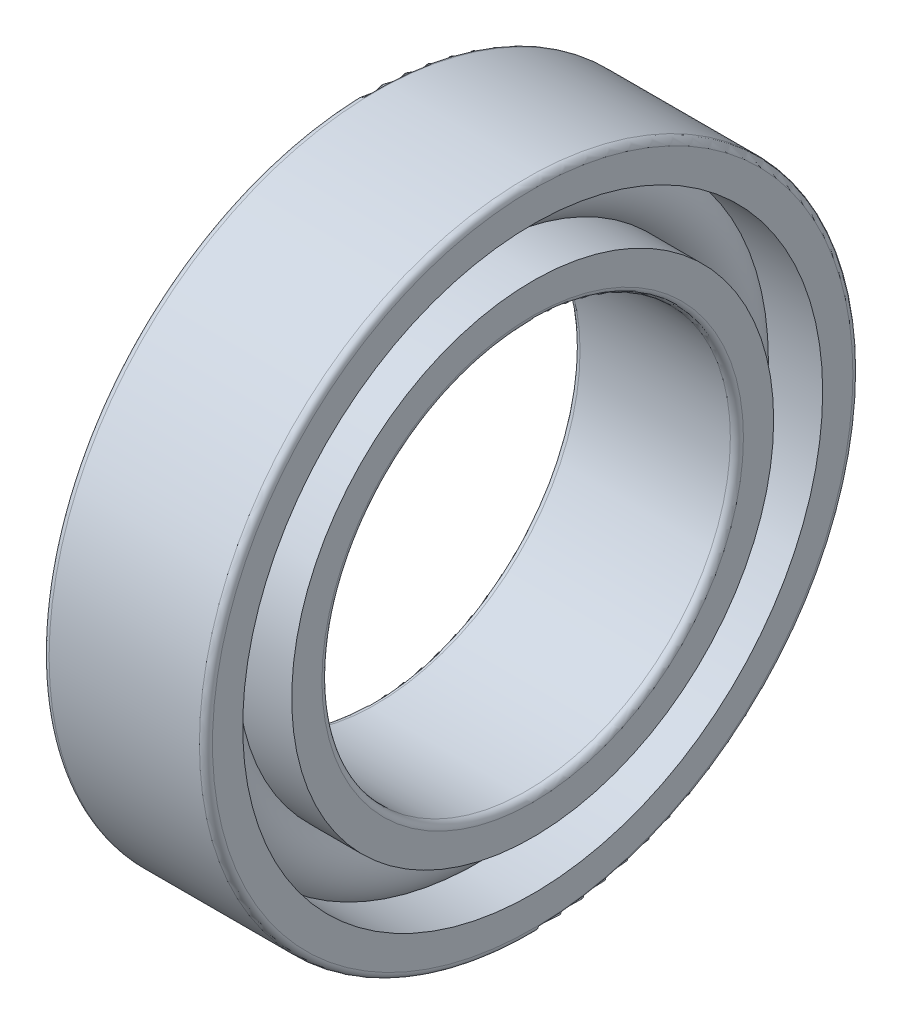
SolidWorks part; units mm, degrees
ref_plane "Plane1" through (0, 0, 0) normal (0, 0, 1) x (1, 0, 0)
ref_plane "Plane2" through (0, 0, 0) normal (0, 1, 0) x (1, 0, 0)
ref_plane "Plane3" through (0, 0, 0) normal (1, 0, 0) x (0, 0, -1)
other "Configuration Table"
sketch "Clipboard" plane through (0, 0, 0) normal (0, 0, 1) x (1, 0, 0)
  line L0 (-10, 0) -> (10, 0) construction
  line L1 (0, 0) -> (22.3471, -0.7804)
  line L2 (0, 0) -> (3.248, 0.1134)
  line L3 (0, 0) -> (22.3471, -0.7804)
  line L4 (0, 0) -> (-22.3573, -0.3902)
  dimension "BallCLRad" = 3.25
sketch "CagSpiSke" plane through (0, 0, 0) normal (0, 0, 1) x (1, 0, 0)
  line L0 (0.045, 3.175) -> (0.045, 3.325)
  line L1 (0.045, 3.325) -> (-0.045, 3.325)
  line L2 (-0.045, 3.325) -> (-0.045, 3.175)
  line L3 (-0.045, 3.175) -> (0.045, 3.175)
  line L4 (-20.6375, 0) -> (20.6375, 0) construction
  line L5 (0, 0) -> (0, 23.7692) construction
  dimension "OD" = 6.65
  dimension "ID" = 6.35
revolve "CageSpine" add sketch "CagSpiSke" angle 0.001 about L4 reverse direction yes
ref_axis "Axis1" through (-50, 0, 0) along (1, 0, 0)
sketch "CagBalSke" plane through (0, 0, 0) normal (0, 0, 1) x (1, 0, 0)
  line L0 (-0.495, 3.25) -> (0.495, 3.25)
  line L1 (-1.905, 3.25) -> (1.905, 3.25) construction
  line L2 (-10, 0) -> (10, 0) construction
  line L3 (0, 0) -> (0, 24) construction
  arc A0 (0.495, 3.25) -> (-0.495, 3.25) centre (0, 3.25) cw
  dimension "BallCLRad" = 3.25
revolve "CageBall" [suppressed] add sketch "CagBalSke" angle 360 about L1 reverse direction yes
pattern_circular "CageBalls" [suppressed] count 2 every 180 about axis through (-50, 0, 0) along (1, 0, 0)
sketch "CagTrmODSke" plane through (0, 0, 0) normal (0, 0, 1) x (1, 0, 0)
  line L0 (0.496, 3.325) -> (0.496, 3.746)
  line L1 (0.496, 3.746) -> (-0.496, 3.746)
  line L2 (-0.496, 3.746) -> (-0.496, 3.325)
  line L3 (-0.496, 3.325) -> (0.496, 3.325)
  line L4 (-20.6375, 0) -> (20.6375, 0) construction
  line L5 (0, 0) -> (0, 25) construction
  dimension "Width" = 0.992
  dimension "ID" = 6.65
  dimension "OD" = 7.492
revolve "CageTrimOD" [suppressed] cut sketch "CagTrmODSke" angle 360 about L4 reverse direction yes
sketch "CagTrmIDSke" plane through (0, 0, 0) normal (0, 0, 1) x (1, 0, 0)
  line L0 (0.496, 2.756) -> (0.496, 3.175)
  line L1 (0.496, 3.175) -> (-0.496, 3.175)
  line L2 (-0.496, 3.175) -> (-0.496, 2.756)
  line L3 (-0.496, 2.756) -> (0.496, 2.756)
  line L4 (-20.6375, 0) -> (20.6375, 0) construction
  line L5 (0, 0) -> (0, 25) construction
  dimension "Width" = 0.992
  dimension "ID" = 5.512
  dimension "OD" = 6.35
revolve "CageTrimID" [suppressed] cut sketch "CagTrmIDSke" angle 360 about L4 reverse direction yes
sketch "BalSimSke" plane through (0, 0, 0) normal (0, 0, 1) x (1, 0, 0)
  line L0 (-10, 0) -> (10, 0) construction
  line L1 (-10, 3.25) -> (10, 3.25) construction
  line L2 (0, 0) -> (0, 23) construction
  circle A0 centre (0, 3.25) radius 0.45
  dimension "BallCLRad" = 3.25
  dimension "Ball_diameter" = 0.9
revolve "BallsSimplified" add sketch "BalSimSke" angle 360 about L0
sketch "BalDetSke" plane through (0, 0, 0) normal (0, 0, 1) x (1, 0, 0)
  line L0 (-0.45, 3.25) -> (0.45, 3.25)
  line L1 (-1.905, 3.25) -> (1.905, 3.25) construction
  line L2 (0, 0) -> (0, 25) construction
  arc A0 (0.45, 3.25) -> (-0.45, 3.25) centre (0, 3.25) cw
  dimension "BallCLRad" = 3.25
  dimension "Ball_diameter" = 0.9
revolve "BallDetailed" [suppressed] add sketch "BalDetSke" angle 360 about L1 reverse direction yes
sketch "InnRacSke" plane through (0, 0, 0) normal (0, 0, 1) x (1, 0, 0)
  line L0 (-0.301, 2.95) -> (-1, 2.95)
  line L1 (-1, 2.95) -> (-1, 2.58)
  line L2 (-0.92, 2.5) -> (0.92, 2.5)
  line L3 (1, 2.58) -> (1, 2.95)
  line L4 (1, 2.95) -> (0.301, 2.95)
  line L5 (-20.6375, 0) -> (20.6375, 0) construction
  line L6 (0, 0) -> (0, 30) construction
  arc A0 (-1, 2.58) -> (-0.92, 2.5) centre (-0.92, 2.58) ccw
  arc A1 (0.92, 2.5) -> (1, 2.58) centre (0.92, 2.58) ccw
  arc A2 (0.301, 2.95) -> (-0.301, 2.95) centre (0, 3.25) cw
  dimension "BallCLRad" = 3.25
  dimension "Fillet_radius" = 0.08
  dimension "Ball_diameter" = 0.85
  dimension "ID" = 5
  dimension "OD" = 5.9
  dimension "Width" = 2
revolve "InnerRace" add sketch "InnRacSke" angle 360 about L5 reverse direction yes
sketch "OutRacSke" plane through (0, 0, 0) normal (0, 0, 1) x (1, 0, 0)
  line L0 (-0.301, 3.55) -> (-1, 3.55)
  line L1 (-1, 3.55) -> (-1, 3.92)
  line L2 (-0.92, 4) -> (0.92, 4)
  line L3 (1, 3.92) -> (1, 3.55)
  line L4 (1, 3.55) -> (0.301, 3.55)
  line L5 (-20.6375, 0) -> (20.6375, 0) construction
  line L6 (0, 0) -> (0, 30) construction
  arc A0 (-1, 3.92) -> (-0.92, 4) centre (-0.92, 3.92) cw
  arc A1 (0.92, 4) -> (1, 3.92) centre (0.92, 3.92) cw
  arc A2 (0.301, 3.55) -> (-0.301, 3.55) centre (0, 3.25) ccw
  dimension "BallCLRad" = 3.25
  dimension "Fillet_radius" = 0.08
  dimension "Ball_diameter" = 0.85
  dimension "Width" = 2
revolve "OuterRace" add sketch "OutRacSke" angle 360 about L5 reverse direction yes
pattern_circular "BallsDetailed" [suppressed] count 2 every 180 about axis through (-50, 0, 0) along (1, 0, 0)
equation "\"BallCLRad@Clipboard\" = ( \"OD@OutRacSke\" + \"ID@InnRacSke\" ) / 4"
equation "\"BallCLRad@BalSimSke\" = \"BallCLRad@Clipboard\""
equation "\"BallCLRad@BalDetSke\" = \"BallCLRad@Clipboard\""
equation "\"BallCLRad@InnRacSke\" = \"BallCLRad@Clipboard\""
equation "\"BallCLRad@OutRacSke\" = \"BallCLRad@Clipboard\""
equation "\"Ball_diameter@InnRacSke\" = \"Ball_diameter@BalDetSke\" - 0.05"
equation "\"Ball_diameter@OutRacSke\" = \"Ball_diameter@BalDetSke\" - 0.05"
equation "\"Ball_diameter@BalSimSke\" = \"Ball_diameter@BalDetSke\""
equation "\"Width@OutRacSke\" = \"Width@InnRacSke\""
equation "\"Fillet_radius@OutRacSke\" = \"Fillet_radius@InnRacSke\""
equation "\"Max_count@Clipboard\" = int( 3.14159265 / atn(( \"Ball_diameter@BalDetSke\" / 2) / sqr( \"BallCLRad@Clipboard\"  *  \"BallCLRad@Clipboard\" - ( \"Ball_diameter@BalDetSke\" / 2) *  ( \"Ball_diameter@BalDetSke\" / 2))))"
equation "\"Max_count@Clipboard\" = ((sgn( \"Max_count@Clipboard\" - \"Count@Clipboard\" )-1)*( \"Max_count@Clipboard\" - \"Count@Clipboard\" ))/-2+ \"Count@Clipboard\""
equation "\"Count@BallsDetailed\" = int( \"Show_count@Clipboard\" ) "
equation "\"Count@BallsDetailed\" = ((sgn( \"Count@BallsDetailed\" - \"Max_count@Clipboard\" )-1)*( \"Count@BallsDetailed\" - \"Max_count@Clipboard\" ))/-2+ \"Max_count@Clipboard\""
equation "\"Count@BallsDetailed\" = ((sgn( \"Count@BallsDetailed\" - \"Min_count@Clipboard\" )+1)*( \"Count@BallsDetailed\" - \"Min_count@Clipboard\"))/2 +\"Min_count@Clipboard\""
equation "\"Angle@BallsDetailed\" = 360.0 / \"Max_count@Clipboard\""
equation "\"BallCLRad@CagBalSke\" = \"BallCLRad@Clipboard\""
equation "\"Count@CageBalls\" = \"Count@BallsDetailed\""
equation "\"Angle@CageBalls\" = \"Angle@BallsDetailed\""
equation "\"Angle@CageSpine\" =  \"Angle@CageBalls\" * ( \"Count@CageBalls\" -1 + int( \"Count@CageBalls\" / \"Max_count@Clipboard\" ) )  + 0.001 -  int( \"Count@CageBalls\" / \"Max_count@Clipboard\" ) * 0.001"
equation "\"Angle@CageSpine\" =  \"Angle@CageSpine\" * int( \"Min_count@Clipboard\" / 2) + int(1 / \"Min_count@Clipboard\")  * 0.001"
equation "\"CageWallOD@CagBalSke\" =  \"Ball_diameter@BalDetSke\" * 1.1"
equation "\"Thickness@CagSpiSke\" =  \"Ball_diameter@BalDetSke\" * 0.1"
equation "\"OD@CagTrmODSke\" = \"BallCLRad@Clipboard\" * 2 + \"CageWallOD@CagBalSke\" + 0.002"
equation "\"ID@CagTrmODSke\" = \"BallCLRad@Clipboard\" * 2 + \"Ball_diameter@BalDetSke\" / 6"
equation "\"OD@CagTrmIDSke\" = \"BallCLRad@Clipboard\" * 2 - \"Ball_diameter@BalDetSke\" / 6"
equation "\"ID@CagTrmIDSke\" = \"BallCLRad@Clipboard\" * 2 - \"CageWallOD@CagBalSke\" + 0.002"
equation "\"OD@CagSpiSke\" = \"ID@CagTrmODSke\""
equation "\"ID@CagSpiSke\" = \"OD@CagTrmIDSke\""
equation "\"Width@CagTrmODSke\" = \"CageWallOD@CagBalSke\" + 0.002"
equation "\"Width@CagTrmIDSke\" = \"CageWallOD@CagBalSke\" + 0.002"
